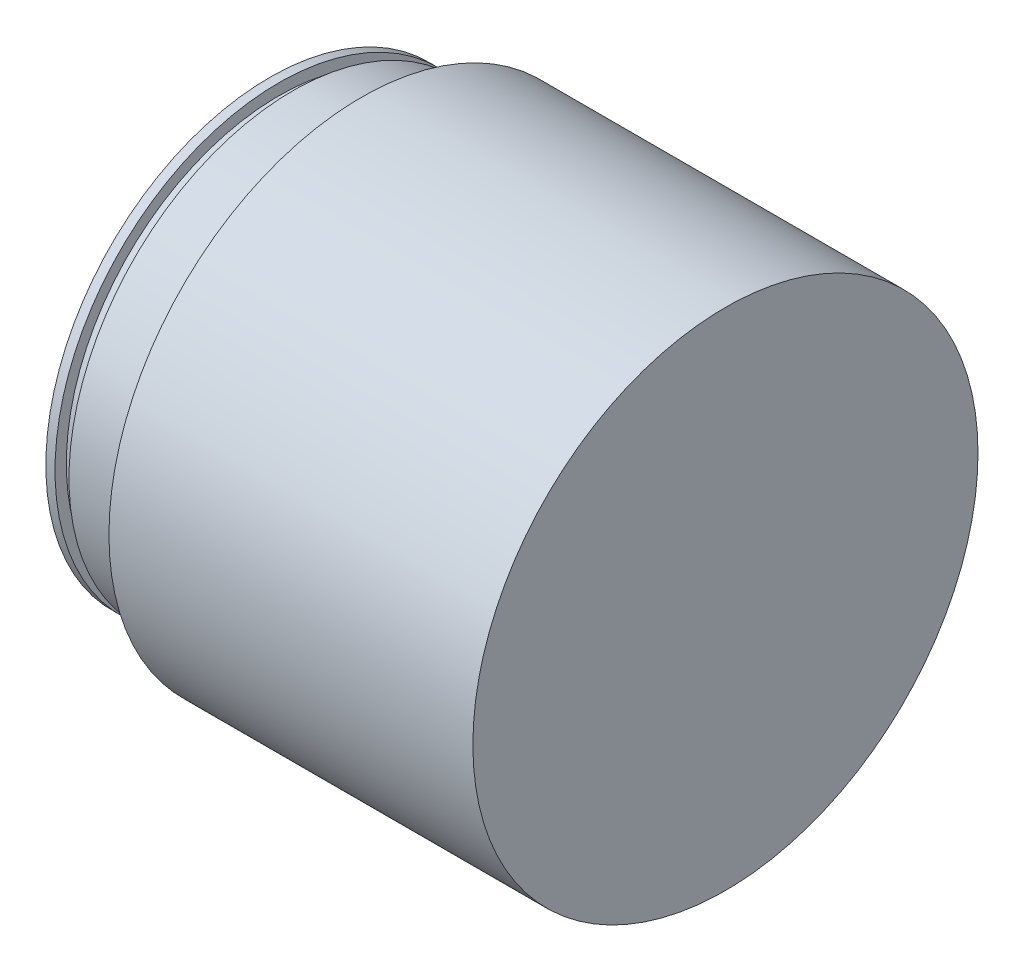
SolidWorks part; units mm, degrees
note: The reader was unsure of these and kept them because the rebuilt part matched: shared geometry of "Bolt Circle Pattern<2>".
material "7075-T6 (SN)"
ref_plane "Front Plane" through (0, 0, 0) normal (0, 0, 1) x (1, 0, 0)
ref_plane "Top Plane" through (0, 0, 0) normal (0, 1, 0) x (1, 0, 0)
ref_plane "Right Plane" through (0, 0, 0) normal (1, 0, 0) x (0, 0, -1)
sketch "Sketch2" plane through (0, 0, 0) normal (0, 0, 1) x (1, 0, 0)
  line L0 (0, 0) -> (0, -30.9499)
  line L1 (0, -30.9499) -> (12.7, -30.9499)
  line L2 (12.7, -30.9499) -> (12.7, 0)
  line L3 (12.7, 0) -> (3.2004, 0)
  line L4 (11.9645, -30.9499) -> (0.5681, -30.9499) construction
  line L5 (3.2004, 0) -> (3.2004, -1.5621)
  line L6 (0, 0) -> (1.27, 0)
  line L7 (1.27, 0) -> (1.27, -1.5621)
  line L8 (1.27, -1.5621) -> (3.2004, -1.5621)
  dimension "D4" = 1.9304
  dimension "D5" = 0
  dimension "D6" = 58.7756
  dimension "D1" = 61.8998
  dimension "D2" = 12.7
  dimension "D3" = 1.27
revolve "Revolve1" add sketch "Sketch2" angle 360 about L4
sketch "Bolt Circle Pattern" plane through (12.7, 0, 0) normal (1, 0, 0) x (0, 0, -1)
  circle A3 centre (0, -30.9499) radius 4.1021
  circle A4 centre (0, -30.9499) radius 30.9499 construction
  circle A5 centre (0, -30.9499) radius 9.525 construction
  point P49 (9.525, -30.9499)
  point P51 (0, -40.4749)
  point P53 (-9.525, -30.9499)
  point P57 (0, -21.4249)
  dimension "D1" = 8.2042
  dimension "D2" = 19.05
sketch "Sketch4" plane through (12.7, 0, 0) normal (1, 0, 0) x (0, 0, -1)
  circle A0 centre (0, -30.9499) radius 34.925
  circle A1 centre (0, -30.9499) radius 30.9499 construction
  circle A2 centre (0, -30.9499) radius 18.161
  dimension "D1" = 69.85
  dimension "D2" = 36.322
extrude "Boss-Extrude1" add sketch "Sketch4" along normal blind 72.771
sketch "Sketch5" plane through (0, 0, 0) normal (1, 0, 0) x (0, 0, -1)
  line L0 (0, -10.6299) -> (-17.5976, -41.1099) construction
  line L1 (-17.5976, -41.1099) -> (17.5976, -41.1099) construction
  line L2 (17.5976, -41.1099) -> (0, -10.6299) construction
  line L3 (0, -10.6299) -> (0, -41.1099) construction
  line L4 (-17.5976, -41.1099) -> (8.7988, -25.8699) construction
  line L5 (17.5976, -41.1099) -> (-8.7988, -25.8699) construction
  arc A0 (-11.1418, -4.2233) -> (11.1418, -4.2233) centre (0, -10.6299) ccw
  arc A2 (-28.7168, -34.6641) -> (-17.575, -53.9623) centre (0, -30.9499) ccw
  arc A4 (-17.575, -53.9623) -> (-28.7168, -34.6641) centre (-17.5976, -41.1099) ccw
  arc A5 (28.7168, -34.6641) -> (17.575, -53.9623) centre (17.5976, -41.1099) ccw
  arc A6 (17.575, -53.9623) -> (28.7168, -34.6641) centre (0, -30.9499) ccw
  arc A7 (11.1418, -4.2233) -> (-11.1418, -4.2233) centre (0, -30.9499) ccw
  dimension "D2" = 12.8524
  dimension "D6" = 12.8524
  dimension "D5" = 12.8524
  dimension "D9" = 28.956
  dimension "D1" = 20.32
  dimension "D3" = 20.32
  dimension "D4" = 20.32
  dimension "D7" = 35.1953
  dimension "D8" = 35.1953
extrude "Cut-Extrude2" cut sketch "Sketch5" along normal up to next from offset 21.75
fillet "Tripod walls" radius 3.175 6 edges at (53.6105, -53.9623, 17.575) (53.6105, -34.6641, 28.7168) (53.6105, -34.6641, -28.7168) (53.6105, -53.9623, -17.575) (53.6105, -4.2233, 11.1418) (53.6105, -4.2233, -11.1418)
fillet "Tripod Face" radius 3.175 15 edges at (21.75, -11.1542, 12.8417) (21.75, -11.1542, -12.8417) (21.75, -4.425, 11.0344) (21.75, -4.425, -11.0344) (21.75, -51.969, -10.7227) (21.75, -29.7265, -23.5644) (21.75, -51.969, 10.7227) (21.75, -29.7265, 23.5644) (21.75, -1.9939, 0) (21.75, -45.4279, -25.0766) (21.75, -45.4279, 25.0766) (21.75, -53.7684, -17.454) (21.75, -34.6563, -28.4884) (21.75, -34.6563, 28.4884) (21.75, -53.7684, 17.454)
ref_plane "Plane1" through (60.071, 0, 0) normal (1, 0, 0) x (0, 0, -1)
ref_plane "Plane2" through (66.421, 0, 0) normal (1, 0, 0) x (0, 0, -1)
split line "Split Line1" [suppressed]
sketch "Sketch12" plane through (85.471, 0, 0) normal (1, 0, 0) x (0, 0, -1)
  line L0 (-21.997, -18.2499) -> (21.997, -18.2499) construction
  line L1 (21.997, -18.2499) -> (0, -56.3499) construction
  line L2 (0, -56.3499) -> (-21.997, -18.2499) construction
  circle A0 centre (0, -30.9499) radius 25.4 construction
  circle A4 centre (-21.997, -18.2499) radius 3.175
  circle A9 centre (21.997, -18.2499) radius 3.175
  circle A12 centre (0, -56.3499) radius 3.175
  dimension "D2" = 6.35
  dimension "D1" = 50.8
extrude "Cut-Extrude3" cut sketch "Sketch12" against normal blind 63.5
sketch "Sketch13" plane through (85.471, 0, 0) normal (1, 0, 0) x (0, 0, -1)
  circle A1 centre (0, -30.9499) radius 34.925
  circle A2 centre (0, -30.9499) radius 34.925
  dimension "D1" = 0
extrude "Cut-Extrude4" cut sketch "Sketch13" against normal offset from surface (22.446 mm away) 41.275 up to face at (21.75, -41.4593, -18.2029)
fillet "Fillet6" [suppressed] radius 2.54
ref_plane "Plane5" through (24.925, 0, 0) normal (1, 0, 0) x (0, 0, -1)
split line "Split Line4"
ref_plane "Plane3" through (47.15, 0, 0) normal (1, 0, 0) x (0, 0, -1)
split line "Split Line2"
ref_plane "Plane4" through (50.325, 0, 0) normal (1, 0, 0) x (0, 0, -1)
split line "Split Line3"
sketch "Sketch16" plane through (0, 0, 0) normal (-1, 0, 0) x (0, 0, 1)
  circle A0 centre (0, -30.9499) radius 22.86
  circle A1 centre (0, -30.9499) radius 30.9499 construction
  dimension "D1" = 45.72
extrude "Compensating Spacing" add sketch "Sketch16" along normal blind 1.016
hole_wizard "1/4 (0.2500) Dowel Hole1" positions "Bolt Circle Pattern" profile "Sketch15" hole size "1/4" standard "ANSI Inch" end condition through all
sketch "Sketch15" plane through (12.7, -21.4249, 0) normal (0, 1, 0) x (0, 0, -1)
  line L0 (0, 0) -> (0, 13.716)
  line L1 (0, 13.716) -> (3.175, 13.716)
  line L2 (3.175, 13.716) -> (3.175, 0)
  line L5 (3.175, 0) -> (0, 0)
  line L11 (0, -6.35) -> (0, 107.95) construction
  dimension "Thru Hole Dia." = 6.35
  dimension "Thru Hole Depth" = 13.716
extrude "5/16 Clearnce" cut sketch "Bolt Circle Pattern<2>" against normal up to surface (13.716 mm away) up to face at (-1.016, -30.9499, -12.7)
sketch "Bolt Circle Pattern<2>" plane through (12.7, 0, 0) normal (1, 0, 0) x (0, 0, -1) same geometry as "Bolt Circle Pattern"
sketch "Sketch17" plane through (12.7, 0, 0) normal (1, 0, 0) x (0, 0, -1)
  circle A0 centre (0, -30.9499) radius 34.925
  circle A1 centre (0, -30.9499) radius 34.925 construction
extrude "Boss-Extrude2" add sketch "Sketch17" along normal up to surface (50.325 mm away) up to face at (63.025, -30.9499, 0)
equation "\"D9@Sketch5\"=2.28/2"
equation "\"D8@Sketch5\"=\"D7@Sketch5\""
equation "\"Drill_Hole\"=0.25"
equation "\"D2@Sketch12\"=\"Drill_Hole\""
